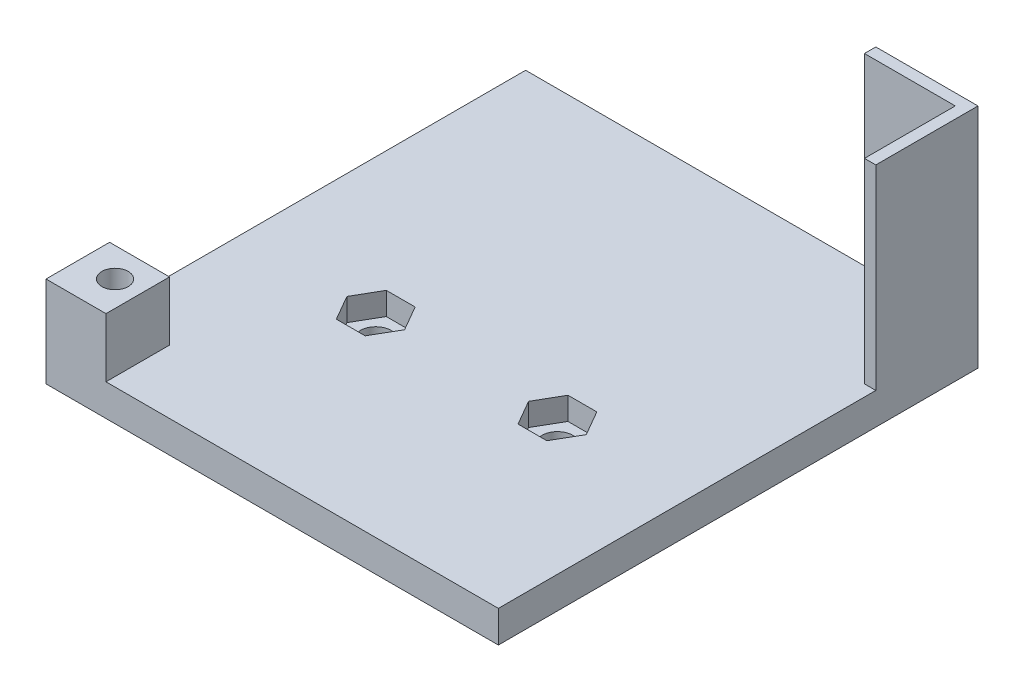
SolidWorks part; units mm, degrees
ref_plane "Front Plane" through (0, 0, 0) normal (0, 0, 1) x (1, 0, 0)
ref_plane "Top Plane" through (0, 0, 0) normal (0, 1, 0) x (1, 0, 0)
ref_plane "Right Plane" through (0, 0, 0) normal (1, 0, 0) x (0, 0, -1)
sketch "Sketch1" plane through (0, 0, 0) normal (0, 1, 0) x (1, 0, 0)
  line L0 (13.65, 26.4) -> (13.65, 25.15)
  line L1 (-24.9, -26.4) -> (24.9, -26.4)
  line L2 (-24.9, -26.4) -> (-24.9, 26.4)
  line L3 (-24.9, 26.4) -> (24.9, 26.4)
  line L4 (24.9, -26.4) -> (24.9, 26.4)
  line L5 (-24.9, -26.4) -> (24.9, 26.4) construction
  line L6 (-24.9, 26.4) -> (24.9, -26.4) construction
  line L7 (13.65, 25.15) -> (23.65, 25.15)
  line L8 (23.65, 25.15) -> (23.65, 15.15)
  line L9 (23.65, 15.15) -> (24.9, 15.15)
  line L11 (-24.9, -26.4) -> (-18.2977, -26.4)
  line L12 (-24.9, -26.4) -> (-24.9, -19.4)
  line L13 (-24.9, -19.4) -> (-18.2977, -19.4)
  line L14 (-18.2977, -26.4) -> (-18.2977, -19.4)
  point P0 (0, 0)
  dimension "D1" = 49.8
  dimension "D2" = 52.8
  dimension "D3" = 10
  dimension "D4" = 7
  dimension "D5" = 1.25
extrude "Boss-Extrude1" add sketch "Sketch1" along normal blind 3.5 contours L9 L8 L7 L0 L3 L2 L1 L4 region at (0.1657, 0, -0.1737)
extrude "Boss-Extrude2" add sketch "Sketch1<4>" along normal blind 25 contours L8 L9 L4 L3 L0 L7 region at (19.275, 0, -26.2409)
sketch "Sketch1<4>" plane through (0, 0, 0) normal (0, 1, 0) x (1, 0, 0) same geometry as "Sketch1"
extrude "Boss-Extrude3" add sketch "Sketch1<5>" along normal blind 10 contours L1 L14 L13 L2 region at (-21.5989, 0, 22.9)
sketch "Sketch1<5>" plane through (0, 0, 0) normal (0, 1, 0) x (1, 0, 0) same geometry as "Sketch1"
sketch "Sketch3" plane through (0, 10, 0) normal (0, 1, 0) x (1, 0, 0)
  line L0 (-24.9, -26.4) -> (-24.9, -19.4) construction
  line L1 (-24.9, -26.4) -> (-18.2977, -26.4) construction
  circle A0 centre (-21.1, -22.6) radius 1.45
  point P2 (0, 0)
  dimension "D3" = 2.9
  dimension "D1" = 3.8
  dimension "D2" = 3.8
extrude "Cut-Extrude1" cut sketch "Sketch3" against normal through all
sketch "Sketch4" plane through (0, 3.5, 0) normal (0, 1, 0) x (1, 0, 0)
  line L0 (-10, -5) -> (10, -5) construction
  line L1 (-6.8246, -5) -> (-8.4123, -2.25)
  line L2 (-8.4123, -2.25) -> (-11.5877, -2.25)
  line L3 (-11.5877, -2.25) -> (-13.1754, -5)
  line L4 (-13.1754, -5) -> (-11.5877, -7.75)
  line L5 (-11.5877, -7.75) -> (-8.4123, -7.75)
  line L6 (-8.4123, -7.75) -> (-6.8246, -5)
  line L7 (13.1754, -5) -> (11.5877, -2.25)
  line L8 (11.5877, -2.25) -> (8.4123, -2.25)
  line L9 (8.4123, -2.25) -> (6.8246, -5)
  line L10 (6.8246, -5) -> (8.4123, -7.75)
  line L11 (8.4123, -7.75) -> (11.5877, -7.75)
  line L12 (11.5877, -7.75) -> (13.1754, -5)
  circle A0 centre (-10, -5) radius 2.75 construction
  circle A1 centre (10, -5) radius 2.75 construction
  circle A2 centre (-10, -5) radius 1.7
  circle A3 centre (10, -5) radius 1.7
  point P9 (0, -5)
  dimension "D3" = 5.5
  dimension "D6" = 3.4
  dimension "D1" = 20
  dimension "D2" = 5
  dimension "D4" = 120
  dimension "D5" = 120
extrude "Cut-Extrude2" cut sketch "Sketch4" against normal through all contours A2 | A3
extrude "Cut-Extrude3" cut sketch "Sketch4<3>" against normal blind 2.5
sketch "Sketch4<3>" plane through (0, 3.5, 0) normal (0, 1, 0) x (1, 0, 0) same geometry as "Sketch4"
